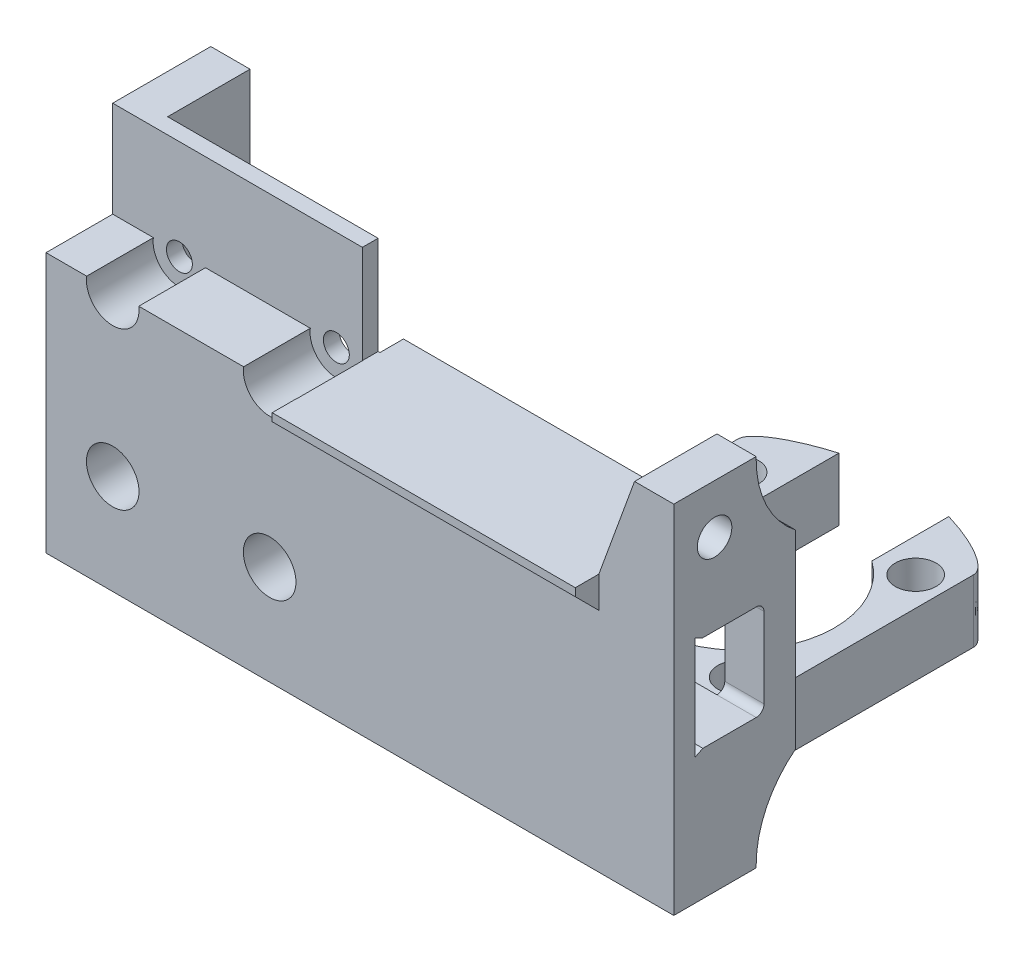
SolidWorks part; units mm, degrees
ref_plane "Front Plane" through (0, 0, 0) normal (0, 0, 1) x (1, 0, 0)
ref_plane "Top Plane" through (0, 0, 0) normal (0, 1, 0) x (1, 0, 0)
ref_plane "Right Plane" through (0, 0, 0) normal (1, 0, 0) x (0, 0, -1)
sketch "Sketch1" plane through (0, 0, 0) normal (0, 0, 1) x (1, 0, 0)
  line L1 (0, 0) -> (80, 0)
  line L2 (0, 0) -> (0, 45.4)
  line L3 (0, 45.4) -> (80, 45.4)
  line L4 (80, 0) -> (80, 45.4)
  line L5 (8.5, 32.7) -> (28.5, 32.7) construction
  line L6 (8.5, 32.7) -> (8.5, 12.7) construction
  line L7 (8.5, 12.7) -> (28.5, 12.7) construction
  line L8 (28.5, 32.7) -> (28.5, 12.7) construction
  circle A0 centre (8.5, 32.7) radius 1.65
  circle A1 centre (28.5, 32.7) radius 1.65
  circle A2 centre (28.5, 12.7) radius 1.65
  circle A3 centre (8.5, 12.7) radius 1.65
  dimension "D3" = 3.3
  dimension "D1" = 45.4
  dimension "D2" = 80
  dimension "D4" = 12.7
  dimension "D5" = 20
  dimension "D6" = 8.5
extrude "Boss-Extrude1" add sketch "Sketch1" along normal blind 10.5
sketch "Sketch2" plane through (0, 0, 0) normal (0, 0, -1) x (-1, 0, 0)
  line L0 (0, 0) -> (-80, 0) construction
  line L1 (0, 45.4) -> (-5, 45.4)
  line L2 (0, 45.4) -> (0, 0)
  line L3 (0, 0) -> (-5, 0)
  line L4 (-5, 45.4) -> (-5, 0)
  dimension "D1" = 5
extrude "Boss-Extrude2" add sketch "Sketch2" along normal blind 10.5
sketch "Sketch3" plane through (0, 0, 0) normal (0, 0, 1) x (1, 0, 0)
  line L0 (80, 0) -> (80, 45.4) construction
  line L1 (80, 28.8) -> (0, 28.8)
  line L2 (80, 28.8) -> (80, 16.6)
  line L3 (80, 16.6) -> (0, 16.6)
  line L4 (0, 28.8) -> (0, 16.6)
  line L5 (0, 0) -> (0, 45.4) construction
  line L6 (80, 22.7) -> (0, 22.7) construction
  point P10 (80, 22.7)
  dimension "D1" = 12.2
extrude "Cut-Extrude1" cut sketch "Sketch3" against normal through all and the other way blind 7.8
sketch "Sketch4" plane through (0, 0, 0) normal (0, 0, -1) x (-1, 0, 0)
  line L1 (-69.5, 0) -> (-39.5, 0)
  line L2 (-69.5, 0) -> (-69.5, 8)
  line L3 (-69.5, 8) -> (-39.5, 8)
  line L4 (-39.5, 0) -> (-39.5, 8)
  line L7 (-5, 0) -> (-80, 0) construction
  dimension "D1" = 8
  dimension "D2" = 30
  dimension "D3" = 39.5
extrude "Boss-Extrude3" add sketch "Sketch4" along normal blind 44.2
sketch "Sketch5" plane through (0, 8, 0) normal (0, 1, 0) x (1, 0, 0)
  line L0 (69.5, 44.2) -> (69.5, 0) construction
  line L1 (80, 0) -> (5, 0) construction
  circle A0 centre (54.4956, 23.5) radius 12
  dimension "D1" = 24
  dimension "D2" = 15.0044
  dimension "D3" = 23.5
extrude "Cut-Extrude2" cut sketch "Sketch5" against normal blind 45
sketch "Sketch6" plane through (0, 16.6, 0) normal (0, -1, 0) x (1, 0, 0)
  circle A3 centre (54.4956, -39.2013) radius 2.6
  circle A4 centre (65.8093, -34.515) radius 2.6
  circle A5 centre (43.1819, -34.515) radius 2.6
  circle A6 centre (43.1819, -11.8876) radius 2.6
  circle A7 centre (65.8093, -11.8876) radius 2.6
  dimension "D1" = 5.2
extrude "Cut-Extrude3" cut sketch "Sketch6" against normal through all both and the other way through all
fillet "Fillet1" radius 6 2 edges at (39.5, 4, -44.2) (69.5, 4, -44.2) second distance 15 conic rho 0.3 first distance on face at (39.5, 4, -22.1) first distance on face at (69.5, 4, -22.1)
sketch "Sketch8" plane through (0, 0, 10.5) normal (0, 0, 1) x (1, 0, 0)
  circle A0 centre (8.5, 32.7) radius 3.35
  circle A1 centre (28.5, 32.7) radius 3.35
  circle A2 centre (8.5, 12.7) radius 3.35
  circle A3 centre (28.5, 12.7) radius 3.35
  dimension "D1" = 6.7
extrude "Cut-Extrude5" cut sketch "Sketch8" against normal offset from surface (8.5 mm away) 2 up to face at (10.15, 12.7, 0)
sketch "Sketch12" plane through (0, 0, 10.5) normal (0, 0, 1) x (1, 0, 0)
  line L0 (80, 45.4) -> (0, 45.4) construction
  line L5 (0, 45.4) -> (45, 45.4)
  line L6 (0, 45.4) -> (0, 33.15)
  line L7 (0, 33.15) -> (45, 33.15)
  line L8 (45, 45.4) -> (45, 33.15)
  line L9 (0, 45.4) -> (0, 0) construction
  dimension "D1" = 12.25
  dimension "D2" = 45
extrude "Cut-Extrude8" cut sketch "Sketch12" against normal offset from surface (8.5 mm away) 2 up to face at (10.15, 32.7, 0)
sketch "Sketch13" plane through (0, 8, 0) normal (0, 1, 0) x (1, 0, 0)
  line L1 (61.4956, 50.8384) -> (47.4956, 50.8384)
  line L2 (61.4956, 50.8384) -> (61.4956, 27.5643)
  line L3 (61.4956, 27.5643) -> (47.4956, 27.5643)
  line L4 (47.4956, 50.8384) -> (47.4956, 27.5643)
  line L5 (61.4956, 50.8384) -> (47.4956, 27.5643) construction
  line L6 (61.4956, 27.5643) -> (47.4956, 50.8384) construction
  point P0 (54.4956, 39.2013)
  dimension "D1" = 14
extrude "Cut-Extrude10" cut sketch "Sketch13" against normal blind 10
sketch "Sketch14" plane through (0, 0, 0) normal (0, 0, -1) x (-1, 0, 0)
  line L1 (-80, 28.8) -> (0, 28.8)
  line L2 (-80, 28.8) -> (-80, 16.6)
  line L3 (-80, 16.6) -> (0, 16.6)
  line L4 (0, 28.8) -> (0, 16.6)
extrude "Boss-Extrude5" [suppressed] add sketch "Sketch14" against normal blind 0.5
sketch "Sketch15" plane through (0, 8, 0) normal (0, 1, 0) x (1, 0, 0)
  circle A0 centre (54.4956, 7.2013) radius 2.75
  dimension "D1" = 5.5
extrude "Boss-Extrude6" add sketch "Sketch15" along normal blind 2
sketch "Sketch16" plane through (0, 45.4, 0) normal (0, 1, 0) x (1, 0, 0)
  line L0 (39.5, 0) -> (69.5, 0) construction
  line L1 (75, 0) -> (31.8196, 0)
  line L2 (75, 0) -> (75, -10.5)
  line L3 (75, -10.5) -> (31.8196, -10.5)
  line L4 (31.8196, 0) -> (31.8196, -10.5)
  line L5 (80, -10.5) -> (45, -10.5) construction
  line L6 (80, -10.5) -> (80, 0) construction
  line L7 (31.8196, -10.5) -> (31.8196, -2) construction
  dimension "D2" = 5
extrude "Cut-Extrude11" cut sketch "Sketch16" against normal blind 12.5
chamfer "Chamfer2" distance 12.5 angle 20 1 edges at (75, 32.9, 5.25) first distance on face at (75, 39.15, 5.25)
sketch "Sketch17" plane through (80, 0, 0) normal (1, 0, 0) x (0, 0, -1)
  line L0 (-10.5, 45.4) -> (0, 45.4) construction
  line L1 (-10.5, 0) -> (-10.5, 45.4) construction
  circle A0 centre (-5.3, 39.15) radius 2.2
  dimension "D1" = 4.4
  dimension "D2" = 6.25
  dimension "D3" = 5.2
extrude "Cut-Extrude12" cut sketch "Sketch17" against normal blind 10
sketch "Sketch18" plane through (80, 0, 0) normal (1, 0, 0) x (0, 0, -1)
  line L0 (-7.8, 28.8) -> (-6.8, 28.8)
  line L1 (-7.8, 28.8) -> (0, 28.8) construction
  line L2 (-6.8, 28.8) -> (-7.8, 29.3)
  line L3 (-7.8, 29.3) -> (-7.8, 28.8)
  line L4 (-7.8, 16.6) -> (-7.8, 16.1)
  line L5 (-7.8, 16.1) -> (-6.8, 16.6)
  line L6 (-7.8, 16.6) -> (0, 16.6) construction
  line L7 (-6.8, 16.6) -> (-7.8, 16.6)
  dimension "D1" = 0.5
  dimension "D2" = 1
  dimension "D3" = 1
  dimension "D4" = 0.5
extrude "Cut-Extrude13" cut sketch "Sketch18" against normal through all
sketch "Sketch19" plane through (0, 0, 0) normal (0, 0, -1) x (-1, 0, 0)
  line L0 (-80, 0) -> (-80, 16.6) construction
  line L1 (-75, 34.8) -> (-80, 34.8)
  line L2 (-75, 34.8) -> (-75, 10.6)
  line L3 (-75, 10.6) -> (-80, 10.6)
  line L4 (-80, 34.8) -> (-80, 10.6)
  line L5 (-5, 16.6) -> (-80, 16.6) construction
  line L6 (-80, 28.8) -> (-5, 28.8) construction
  dimension "D1" = 6
  dimension "D2" = 6
extrude "Boss-Extrude7" add sketch "Sketch19" along normal blind 5
sketch "Sketch20" plane through (80, 0, 0) normal (1, 0, 0) x (0, 0, -1)
  line L0 (0, 28.8) -> (0, 16.6)
  line L1 (0, 28.8) -> (1, 28.8)
  line L2 (0, 16.6) -> (1, 16.6)
  line L3 (1, 28.8) -> (1, 16.6)
  dimension "D1" = 1
extrude "Cut-Extrude14" cut sketch "Sketch20" against normal through all
sketch "Sketch21" plane through (0, 16.6, 0) normal (0, 1, 0) x (1, 0, 0)
  line L0 (5, 0) -> (5, 10.5) construction
  line L1 (0, 10.5) -> (5, 10.5)
  line L2 (0, 10.5) -> (0, 1)
  line L3 (0, 1) -> (5, 1)
  line L4 (5, 10.5) -> (5, 1)
  dimension "D1" = 9.5
extrude "Boss-Extrude8" add sketch "Sketch21" along normal up to surface (12.2 mm away) up to face at (40, 28.8, -1.175)
fillet "Fillet2" radius 1 4 edges at (77.5, 16.6, -1) (77.5, 28.8, -1) (2.5, 16.6, -1) (2.5, 28.8, -1)
fillet "Fillet3" radius 13 2 edges at (77.5, 10.6, 0) (77.5, 34.8, 0)
chamfer "Chamfer1" distance 2 angle 45 1 edges at (54.4956, 10, -4.4513)
sketch "Sketch22" plane through (0, 0, 10.5) normal (0, 0, 1) x (1, 0, 0)
  line L1 (70.4504, 32.9) -> (31.8196, 32.9)
  line L2 (70.4504, 32.9) -> (70.4504, 31.9)
  line L3 (70.4504, 31.9) -> (31.8196, 31.9)
  line L4 (31.8196, 32.9) -> (31.8196, 31.9)
  line L5 (70.4504, 32.9) -> (31.8196, 31.9) construction
  line L6 (70.4504, 31.9) -> (31.8196, 32.9) construction
  line L7 (31.8196, 32.9) -> (31.8196, 45.4) construction
  point P4 (51.135, 32.4)
  dimension "D1" = 1
extrude "Boss-Extrude9" add sketch "Sketch22" along normal blind 3
sketch "Sketch23" plane through (0, 0, 0) normal (0, 0, -1) x (-1, 0, 0)
  line L1 (-70.4504, 32.9) -> (-32.0504, 32.9)
  line L2 (-70.4504, 32.9) -> (-70.4504, 31.9)
  line L3 (-70.4504, 31.9) -> (-32.0504, 31.9)
  line L4 (-32.0504, 32.9) -> (-32.0504, 31.9)
  line L5 (-70.4504, 32.9) -> (-32.0504, 31.9) construction
  line L6 (-70.4504, 31.9) -> (-32.0504, 32.9) construction
  point P4 (-51.2504, 32.4)
  dimension "D1" = 1
  dimension "D2" = 38.4
extrude "Boss-Extrude10" add sketch "Sketch23" along normal blind 3
chamfer "Chamfer3" distance 3 angle 45 2 edges at (51.135, 31.9, 10.5) (51.2504, 31.9, 0)
